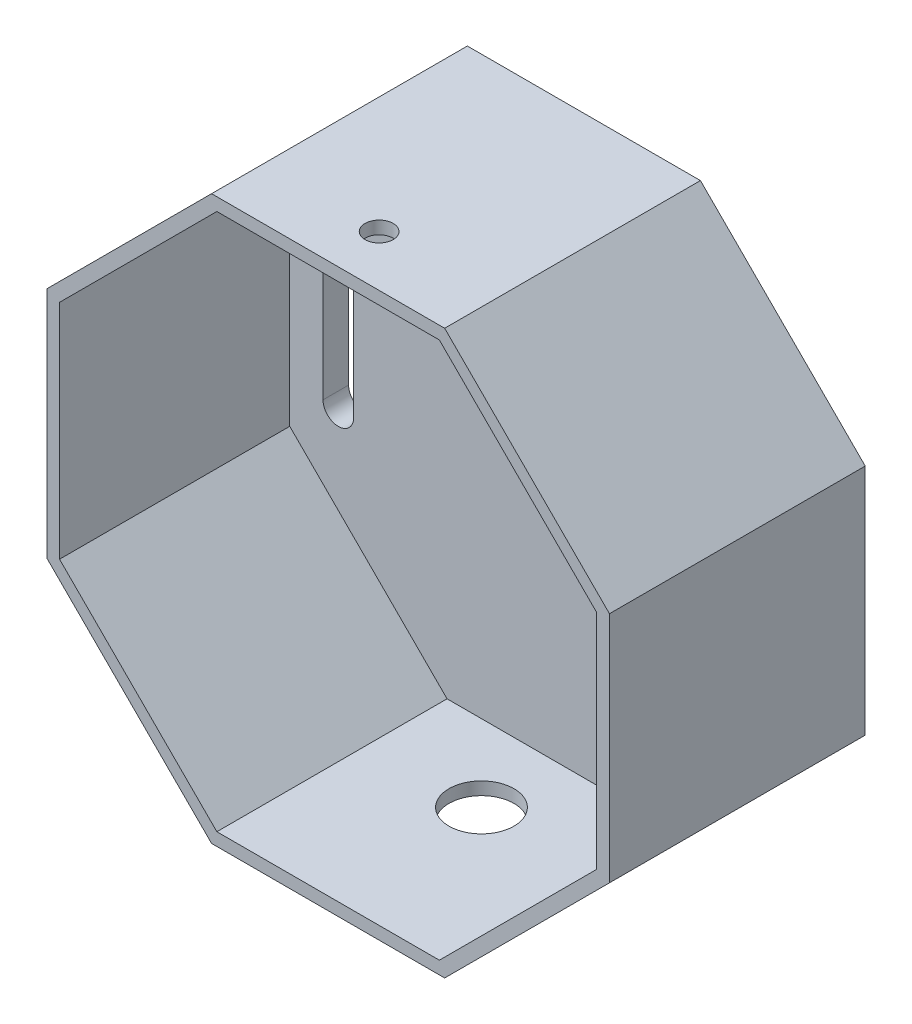
SolidWorks part; units mm, degrees
material "ABS PC"
ref_plane "Front Plane" through (0, 0, 0) normal (0, 0, 1) x (1, 0, 0)
ref_plane "Top Plane" through (0, 0, 0) normal (0, 1, 0) x (1, 0, 0)
ref_plane "Right Plane" through (0, 0, 0) normal (1, 0, 0) x (0, 0, -1)
sketch "Sketch8" plane through (0, 0, 0) normal (0, 0, 1) x (1, 0, 0)
  line L1 (55, 22.7817) -> (22.7817, 55)
  line L2 (22.7817, 55) -> (-22.7817, 55)
  line L3 (-22.7817, 55) -> (-55, 22.7817)
  line L4 (-55, 22.7817) -> (-55, -22.7817)
  line L5 (-55, -22.7817) -> (-22.7817, -55)
  line L6 (-22.7817, -55) -> (22.7817, -55)
  line L7 (22.7817, -55) -> (55, -22.7817)
  line L8 (55, -22.7817) -> (55, 22.7817)
  circle A0 centre (0, 0) radius 55 construction
extrude "Boss-Extrude3" add sketch "Sketch8" along normal blind 50
sketch "Sketch9" plane through (0, 0, 50) normal (0, 0, 1) x (1, 0, 0)
  line L1 (52.5, 21.7462) -> (21.7462, 52.5)
  line L2 (21.7462, 52.5) -> (-21.7462, 52.5)
  line L3 (-21.7462, 52.5) -> (-52.5, 21.7462)
  line L4 (-52.5, 21.7462) -> (-52.5, -21.7462)
  line L5 (-52.5, -21.7462) -> (-21.7462, -52.5)
  line L6 (-21.7462, -52.5) -> (21.7462, -52.5)
  line L7 (21.7462, -52.5) -> (52.5, -21.7462)
  line L8 (52.5, -21.7462) -> (52.5, 21.7462)
  circle A0 centre (0, 0) radius 52.5 construction
extrude "Cut-Extrude3" cut sketch "Sketch9" against normal blind 45
hole_wizard "Antenna Hole" positions "Sketch10" profile "Sketch12" legacy end condition through all
sketch "Sketch10" plane through (0, -52.5, 0) normal (0, 1, 0) x (1, 0, 0)
  point P0 (0, -20.0175)
sketch "Sketch12" plane through (0, -52.5, 20.0175) normal (1, 0, 0) x (0, 0, 1)
  line L0 (0, 0) -> (0, 2.5)
  line L1 (0, 2.5) -> (6.35, 2.5)
  line L2 (6.35, 2.5) -> (6.35, 0)
  line L3 (6.35, 0) -> (0, 0)
  line L4 (0, 110) -> (0, -10) construction
  dimension "Diameter" = 12.7
  dimension "Depth" = 2.5
sketch "Sketch15" plane through (0, 0, 0) normal (0, 0, -1) x (-1, 0, 0)
  line L0 (-43, 13.2597) -> (-43, -13.2907) construction
  line L1 (-40, 13.2597) -> (-40, -13.2907)
  line L2 (-46, 13.2597) -> (-46, -13.2907)
  line L3 (-52.5, -21.7462) -> (-52.5, 21.7462) construction
  arc A0 (-40, 13.2597) -> (-46, 13.2597) centre (-43, 13.2597) ccw
  arc A1 (-46, -13.2907) -> (-40, -13.2907) centre (-43, -13.2907) ccw
  point P2 (-43, -0.0155)
  point P7 (-46, -0.0155)
  dimension "D1" = 6.5
extrude "Right GPIO Slot" cut sketch "Sketch15" against normal blind 5 and the other way through all
sketch "Sketch18" plane through (0, 0, 0) normal (0, 0, -1) x (-1, 0, 0)
  line L0 (43, 12.9852) -> (43, -14.0148) construction
  line L1 (46, 12.9852) -> (46, -14.0148)
  line L2 (40, 12.9852) -> (40, -14.0148)
  line L3 (52.5, 21.7462) -> (52.5, -21.7462) construction
  arc A0 (46, 12.9852) -> (40, 12.9852) centre (43, 12.9852) ccw
  arc A1 (40, -14.0148) -> (46, -14.0148) centre (43, -14.0148) ccw
  point P2 (43, -0.5148)
  point P10 (46, -0.5148)
  dimension "D1" = 6.5
extrude "Left GPIO Slot" cut sketch "Sketch18" against normal blind 5
hole_wizard "PV Panel Barrel Jack Hole" positions "Sketch19" profile "Sketch21" legacy end condition up to next
sketch "Sketch19" plane through (0, 55, 0) normal (0, 1, 0) x (1, 0, 0)
  point P0 (0, -40.0311)
  point P3 (0, -40.0311)
sketch "Sketch21" plane through (0, 55, 40.0311) normal (1, 0, 0) x (0, 0, 1)
  line L0 (0, 0) -> (0, 110)
  line L1 (0, 110) -> (2.75, 110)
  line L2 (2.75, 110) -> (2.75, 0)
  line L3 (2.75, 0) -> (0, 0)
  line L4 (0, 110) -> (0, -10) construction
  dimension "Diameter" = 5.5
  dimension "Depth" = 110
